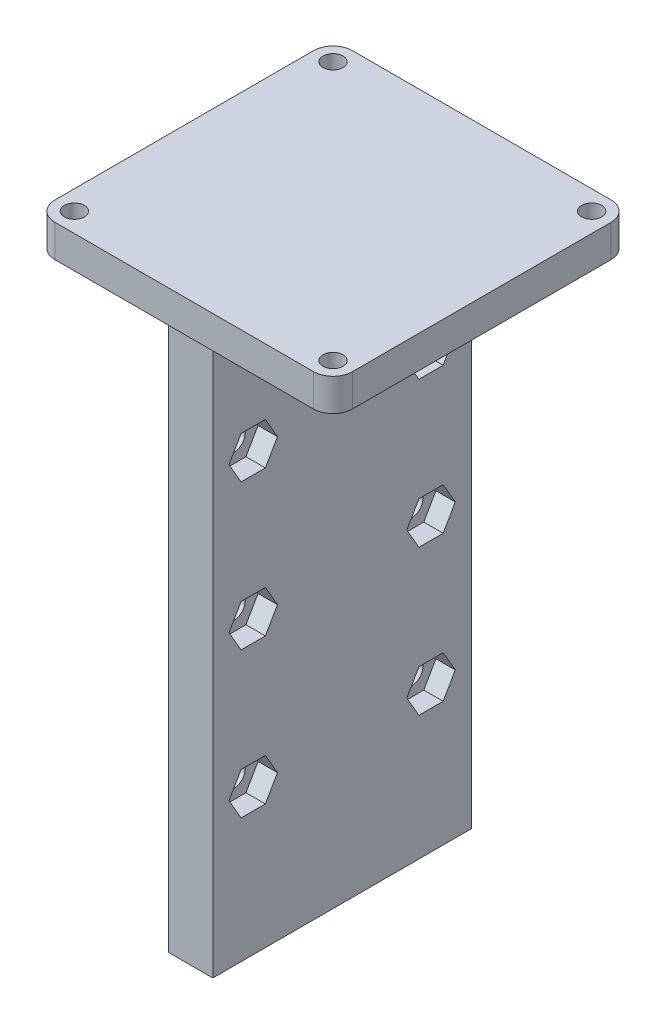
SolidWorks part; units mm, degrees
note: The reader was unsure of these and kept them because the rebuilt part matched: shared geometry of "Sketch2<4>", "Sketch3<4>".
ref_plane "Front Plane" through (0, 0, 0) normal (0, 0, 1) x (1, 0, 0)
ref_plane "Top Plane" through (0, 0, 0) normal (0, 1, 0) x (1, 0, 0)
ref_plane "Right Plane" through (0, 0, 0) normal (1, 0, 0) x (0, 0, -1)
sketch "Sketch2" plane through (0, 0, 0) normal (0, 0, 1) x (1, 0, 0)
  line L0 (0, 90) -> (-14.5875, 90)
  line L1 (0, 0) -> (6.825, 0)
  line L2 (0, 0) -> (0, 90)
  line L4 (6.825, 0) -> (6.825, 90)
  line L5 (-14.5875, 90) -> (-14.5875, 95)
  line L6 (-14.5875, 95) -> (31.4125, 95)
  line L7 (31.4125, 95) -> (31.4125, 90)
  line L8 (31.4125, 90) -> (13.005, 90)
  line L9 (6.825, 90) -> (10, 90)
  line L10 (6.825, 90) -> (10.005, 90)
  line L11 (10.005, 90) -> (10.005, 87)
  line L12 (10.005, 87) -> (13.005, 90)
  line L13 (10, 90) -> (10, 0) construction
  line L14 (10, 0) -> (6.825, 0) construction
  line L15 (10.005, 90) -> (6.825, 90)
  line L16 (0, 90) -> (6.825, 90)
  line L17 (10.005, 90) -> (13.005, 90)
  point P12 (8.4125, 90)
  dimension "D1" = 6.825
  dimension "D2" = 90
  dimension "D3" = 23
  dimension "D4" = 5
  dimension "D5" = 23
  dimension "D6" = 3.175
  dimension "D7" = 3.18
  dimension "D8" = 3
  dimension "D9" = 3
extrude "Sleeve_Outline" add sketch "Sketch2" along normal blind 46 contours L10 L17 L8 L7 L6 L5 L0 L16 L9
extrude "Beam_Mounting" add sketch "Sketch2<4>" along normal blind 40 contours L16 L2 L1 L4 | L17 L11 L12
sketch "Sketch2<4>" plane through (0, 0, 0) normal (0, 0, 1) x (1, 0, 0) same geometry as "Sketch2"
sketch "Sketch3" plane through (6.825, 0, 0) normal (1, 0, 0) x (0, 0, -1)
  line L0 (-40, 0) -> (-37.5, 0)
  line L1 (-40, 0) -> (0, 0) construction
  line L2 (-40, 0) -> (-40, 90) construction
  line L3 (-37.5, 0) -> (-30, 0)
  line L4 (-37.5, 0) -> (-37.5, 90) construction
  line L5 (-46, 90) -> (0, 90) construction
  line L6 (-30, 0) -> (-30, 90) construction
  line L7 (-40, 45) -> (0, 45) construction
  line L8 (0, 0) -> (0, 90) construction
  line L9 (-37.5, 45) -> (-30, 45) construction
  line L10 (-37.5, 45) -> (-30, 45) construction
  line L11 (-30, 45) -> (-33.75, 45) construction
  line L12 (-37.5, 90) -> (-37.5, 45) construction
  line L13 (-30, 45) -> (-31.875, 48.2476)
  line L14 (-31.875, 48.2476) -> (-35.625, 48.2476)
  line L15 (-35.625, 48.2476) -> (-37.5, 45)
  line L16 (-37.5, 45) -> (-35.625, 41.7524)
  line L17 (-35.625, 41.7524) -> (-31.875, 41.7524)
  line L18 (-31.875, 41.7524) -> (-30, 45)
  line L19 (-37.5, 67.5) -> (0, 67.5) construction
  line L20 (0, 67.5) -> (-41.17, 67.5) construction
  line L21 (-37.5, 45) -> (-37.5, 0) construction
  line L22 (-37.5, 22.5) -> (0, 22.5) construction
  line L23 (-30, 22.5) -> (-33.75, 22.5) construction
  line L24 (-37.5, 22.5) -> (-35.625, 19.2524)
  line L25 (-37.5, 22.5) -> (-30, 22.5) construction
  line L26 (-35.625, 25.7476) -> (-37.5, 22.5)
  line L27 (-31.875, 19.2524) -> (-30, 22.5)
  line L28 (-40, 22.5) -> (0, 22.5) construction
  line L29 (-35.625, 19.2524) -> (-31.875, 19.2524)
  line L30 (-30, 22.5) -> (-31.875, 25.7476)
  line L31 (-31.875, 25.7476) -> (-35.625, 25.7476)
  line L32 (-37.5, 22.5) -> (-30, 22.5) construction
  line L33 (-30, 67.5) -> (-33.75, 67.5) construction
  line L34 (-37.5, 67.5) -> (-35.625, 64.2524)
  line L35 (-37.5, 67.5) -> (-30, 67.5) construction
  line L36 (-35.625, 70.7476) -> (-37.5, 67.5)
  line L37 (-31.875, 64.2524) -> (-30, 67.5)
  line L38 (-40, 67.5) -> (0, 67.5) construction
  line L39 (-35.625, 64.2524) -> (-31.875, 64.2524)
  line L40 (-30, 67.5) -> (-31.875, 70.7476)
  line L41 (-31.875, 70.7476) -> (-35.625, 70.7476)
  line L42 (-37.5, 67.5) -> (-30, 67.5) construction
  line L43 (-40, 0) -> (0, 0) construction
  line L44 (-20, 0) -> (-20, 108.4482) construction
  line L45 (-35.625, 25.7476) -> (-31.875, 25.7476)
  line L46 (-37.5, 22.5) -> (-35.625, 25.7476)
  line L47 (-35.625, 19.2524) -> (-37.5, 22.5)
  line L48 (-31.875, 19.2524) -> (-35.625, 19.2524)
  line L49 (-31.875, 25.7476) -> (-30, 22.5)
  line L50 (-8.125, 70.7476) -> (-4.375, 70.7476)
  line L51 (-8.125, 64.2524) -> (-10, 67.5)
  line L52 (-10, 67.5) -> (-8.125, 70.7476)
  line L53 (-2.5, 67.5) -> (-4.375, 64.2524)
  line L54 (-4.375, 64.2524) -> (-8.125, 64.2524)
  line L55 (-4.375, 70.7476) -> (-2.5, 67.5)
  line L56 (-4.375, 48.2476) -> (-2.5, 45)
  line L57 (-8.125, 48.2476) -> (-4.375, 48.2476)
  line L58 (-10, 45) -> (-8.125, 48.2476)
  line L59 (-8.125, 41.7524) -> (-10, 45)
  line L60 (-4.375, 41.7524) -> (-8.125, 41.7524)
  line L61 (-2.5, 45) -> (-4.375, 41.7524)
  line L62 (-4.375, 25.7476) -> (-2.5, 22.5)
  line L63 (-8.125, 25.7476) -> (-4.375, 25.7476)
  line L64 (-10, 22.5) -> (-8.125, 25.7476)
  line L65 (-8.125, 19.2524) -> (-10, 22.5)
  line L66 (-4.375, 19.2524) -> (-8.125, 19.2524)
  line L67 (-2.5, 22.5) -> (-4.375, 19.2524)
  circle A0 centre (-33.75, 45) radius 3.2476 construction
  circle A1 centre (-33.75, 45) radius 1.75
  circle A2 centre (-33.75, 22.5) radius 3.2476 construction
  circle A3 centre (-33.75, 22.5) radius 1.75
  circle A4 centre (-33.75, 67.5) radius 3.2476 construction
  circle A5 centre (-33.75, 67.5) radius 1.75
  circle A6 centre (-6.25, 67.5) radius 1.75
  circle A7 centre (-6.25, 67.5) radius 3.2476 construction
  circle A8 centre (-6.25, 45) radius 1.75
  circle A9 centre (-6.25, 45) radius 3.2476 construction
  circle A10 centre (-6.25, 22.5) radius 1.75
  circle A11 centre (-6.25, 22.5) radius 3.2476 construction
  dimension "D3" = 3.5
  dimension "D1" = 2.5
  dimension "D2" = 7.5
extrude "Nut_Inserts" cut sketch "Sketch3" against normal blind 3 contours L17 L18 L13 L14 L15 L16 A1 | L30 L31 L26 L24 L29 L27 A3 | A5 | L40 L41 L36 L34 L39 L37 A5 | L55 L50 L52 L51 L54 L53 A6 | L61 L56 L57 L58 L59 L60 A8 | L67 L62 L63 L64 L65 L66 A10
extrude "Screw_Inserts" cut sketch "Sketch3<4>" against normal blind 23 contours A5 | A1 | A3 | A10 | A8 | A6
sketch "Sketch3<4>" plane through (6.825, 0, 0) normal (1, 0, 0) x (0, 0, -1) same geometry as "Sketch3"
sketch "Sketch4" plane through (0, 95, 0) normal (0, 1, 0) x (1, 0, 0)
  line L0 (-14.5875, 0) -> (31.4125, 0) construction
  line L1 (-11.5875, 0) -> (31.4125, 0)
  line L2 (-14.5875, -3) -> (-14.5875, -46)
  line L3 (-14.5875, -46) -> (31.4125, -46)
  line L4 (31.4125, 0) -> (31.4125, -46)
  line L5 (8.4125, 0) -> (8.4125, -53.8097) construction
  line L6 (8.4125, -53.8097) -> (31.4125, -23) construction
  line L7 (31.4125, -23) -> (-36.4157, -23) construction
  arc A0 (-11.5875, 0) -> (-14.5875, -3) centre (-11.5875, -3) ccw
  circle A1 centre (-11.5875, -3) radius 1.55
  arc A2 (28.4125, 0) -> (31.4125, -3) centre (28.4125, -3) cw
  circle A3 centre (28.4125, -3) radius 1.55
  arc A4 (28.4125, -46) -> (31.4125, -43) centre (28.4125, -43) ccw
  circle A5 centre (28.4125, -43) radius 1.55
  arc A6 (-11.5875, -46) -> (-14.5875, -43) centre (-11.5875, -43) cw
  circle A7 centre (-11.5875, -43) radius 1.55
  point P8 (-14.5875, 0)
  line M5 (31.4125, 0) -> (-14.5875, 0)
  line M6 (-14.5875, 0) -> (-14.5875, -46)
  line M7 (-14.5875, -46) -> (31.4125, -46)
  line M8 (31.4125, -46) -> (31.4125, 0)
  dimension "D1" = 3
extrude "Board_Shaping" cut sketch "Sketch4" against normal blind 10 contours A6 L2 M7 | A7 | A1 | A0 M5 M6 | A2 L4 M5 | A3 | A5 | A4 L3 M8
